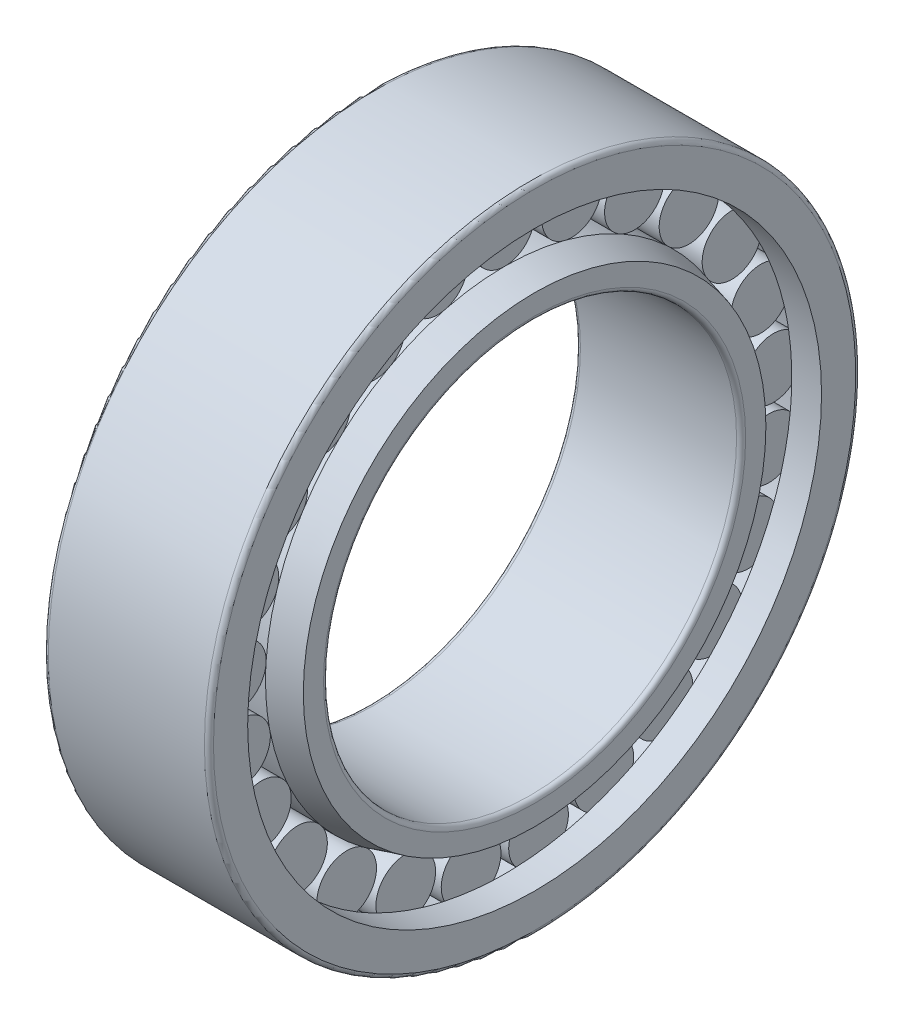
SolidWorks part; units mm, degrees
ref_plane "Front" through (0, 0, 0) normal (0, 0, 1) x (1, 0, 0)
ref_plane "Top" through (0, 0, 0) normal (0, 1, 0) x (1, 0, 0)
ref_plane "Right" through (0, 0, 0) normal (1, 0, 0) x (0, 0, -1)
sketch "Sketch1" plane through (0, 0, 0) normal (0, 0, 1) x (1, 0, 0)
  line L0 (0, 44.0554) -> (0, 70.0073) construction
  line L1 (75.4578, 78.8484) -> (0, 78.8484) construction
  line L2 (78.3629, -78.8484) -> (0, -78.8484) construction
  line L7 (12.7879, 57.9333) -> (20, 56.0008)
  line L8 (-12.7879, 57.9333) -> (12.7879, 57.9333)
  line L9 (-12.7879, 57.9333) -> (-20, 56.0008)
  line L12 (0, 0) -> (78.3067, 0) construction
  line L13 (20, 51.1) -> (20, 56.0008)
  line L14 (-18.9, 50) -> (18.9, 50)
  line L15 (-20, 51.1) -> (-20, 56.0008)
  arc A2 (18.9, 50) -> (20, 51.1) centre (18.9, 51.1) ccw
  arc A3 (-20, 51.1) -> (-18.9, 50) centre (-18.9, 51.1) ccw
  dimension "D1" = 1.1
  dimension "D2" = 40
  dimension "D3" = 15
  dimension "D4" = 100
  dimension "D5" = 115.8666
  dimension "D6" = 7.2121
  dimension "D7" = 157.6968
revolve "Revolve1" add sketch "Sketch1" angle 360 about L12
sketch "Sketch2" plane through (0, 0, 0) normal (0, 0, 1) x (1, 0, 0)
  line L0 (5.4091, 65.1454) -> (-5.4091, 65.1454) construction
  line L2 (12.7879, 57.9333) -> (-12.7879, 57.9333) construction
  line L5 (12.7879, 65.1454) -> (12.7879, 72.3775)
  line L7 (5.4091, 65.1454) -> (5.4091, 72.3775)
  line L8 (5.4091, 72.3775) -> (12.7879, 72.3775)
  line L9 (5.4091, 65.1454) -> (12.7879, 65.1454)
  line L10 (0, 71.4038) -> (0, 54.1434) construction
  line L12 (-12.7879, 65.1454) -> (-12.7879, 72.3775)
  line L13 (-5.4091, 65.1454) -> (-12.7879, 65.1454)
  line L14 (-5.4091, 65.1454) -> (-5.4091, 72.3775)
  line L15 (-5.4091, 72.3775) -> (-12.7879, 72.3775)
  dimension "D2" = 7.2321
  dimension "D3" = 10.8182
  dimension "D4" = 25.5758
  dimension "D1" = 14.4442
revolve "Revolve2" add sketch "Sketch2" angle 360 about L0
sketch "Sketch3" plane through (0, 0, 0) normal (0, 0, 1) x (1, 0, 0)
  line L3 (0, 59.3178) -> (0, 74.7165) construction
  line L4 (-20, 69.4727) -> (-12.7879, 69.4727)
  line L5 (20, 69.4727) -> (20, 77.7484)
  line L6 (-20, 69.4727) -> (-20, 77.7484)
  line L14 (12.7879, 69.4727) -> (12.7879, 72.3575)
  line L15 (12.7879, 72.3575) -> (5.4091, 72.3575)
  line L16 (5.4091, 69.4727) -> (5.4091, 72.3575)
  line L17 (-5.4091, 69.4727) -> (-5.4091, 72.3575)
  line L18 (-12.7879, 69.4727) -> (-12.7879, 72.3575)
  line L19 (-12.7879, 72.3575) -> (-5.4091, 72.3575)
  line L20 (-5.4091, 69.4727) -> (5.4091, 69.4727)
  line L21 (12.7879, 69.4727) -> (20, 69.4727)
  line L22 (0, 0) -> (94.5773, 0) construction
  line L23 (-18.9, 78.8484) -> (18.9, 78.8484)
  arc A2 (20, 77.7484) -> (18.9, 78.8484) centre (18.9, 77.7484) ccw
  arc A3 (-18.9, 78.8484) -> (-20, 77.7484) centre (-18.9, 77.7484) ccw
  dimension "D5" = 1.1
  dimension "D1" = 10.8182
  dimension "D2" = 2.8848
  dimension "D3" = 7.2121
  dimension "D4" = 40
  dimension "D6" = 157.6968
  dimension "D7" = 138.9454
revolve "Revolve3" add sketch "Sketch3" angle 360 about L22
pattern_circular "Circular-Pattern1" count 25 over 360 about axis through (0, 0, 0) along (1, 0, 0) of "Revolve2"
equation "\"D5@Sketch1\"=\"D4@Sketch1\"+11*( \"D7@Sketch1\"-\"D4@Sketch1\")/40"
equation "\"D6@Sketch1\"=( \"D7@Sketch1\"-\"D4@Sketch1\")/8"
equation "\"D1@Sketch2\"=( \"D7@Sketch1\"-\"D4@Sketch1\")/4+0.02"
equation "\"D2@Sketch2\"=(\"D1@Sketch2\"+0.02)/2"
equation "\"D3@Sketch2\"=( \"D7@Sketch1\"-\"D4@Sketch1\")*0.1875"
equation "\"D4@Sketch2\"=\"D2@Sketch1\"-\"D6@Sketch1\"*2"
equation "\"D1@Sketch3\"=\"D3@Sketch2\""
equation "\"D2@Sketch3\"=( \"D7@Sketch1\"-\"D4@Sketch1\")/20"
equation "\"D3@Sketch3\"=\"D6@Sketch1\""
equation "\"D4@Sketch3\"=\"D2@Sketch1\""
equation "\"D5@Sketch3\"=\"D1@Sketch1\""
equation "\"D6@Sketch3\" = \"D7@Sketch1\""
equation "\"D7@Sketch3\"=\"D5@Sketch1\"+(( \"D7@Sketch1\"-\"D4@Sketch1\")/4-\"D2@Sketch3\")*2"
equation "\"D1@Circular-Pattern1\" = int( 3.14159265 / atn(( ( \"D7@Sketch1\"-\"D4@Sketch1\") / 8) / sqr( ( \"D7@Sketch1\"+\"D4@Sketch1\") * ( \"D7@Sketch1\"+\"D4@Sketch1\")/16- ( ( \"D7@Sketch1\"-\"D4@Sketch1\")/8) *  ( ( \"D7@Sketch1\"-\"D4@Sketch1\")/ 2))))-2"
